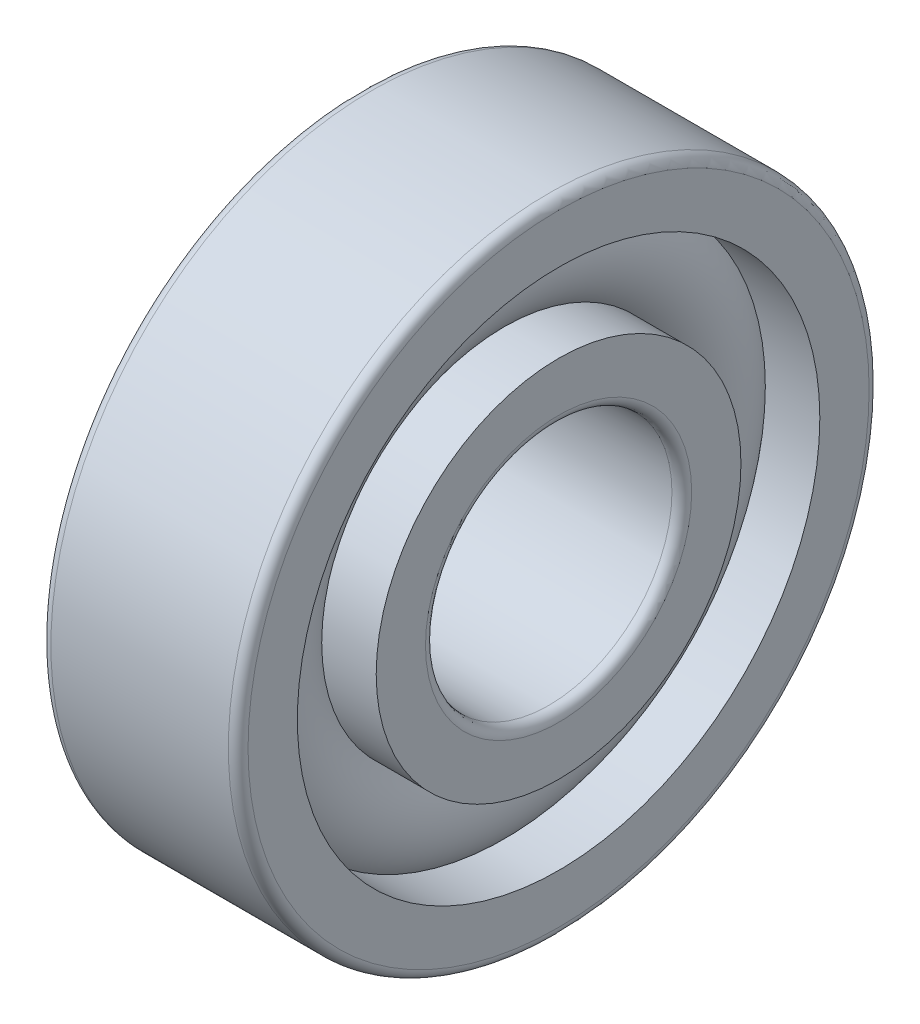
SolidWorks part; units mm, degrees
ref_plane "Plane1" through (0, 0, 0) normal (0, 0, 1) x (1, 0, 0)
ref_plane "Plane2" through (0, 0, 0) normal (0, 1, 0) x (1, 0, 0)
ref_plane "Plane3" through (0, 0, 0) normal (1, 0, 0) x (0, 0, -1)
sketch "Clipboard" plane through (0, 0, 0) normal (0, 0, 1) x (1, 0, 0)
  line L0 (-10, 0) -> (10, 0) construction
  line L1 (0, 0) -> (22.3471, -0.7804)
  line L2 (0, 0) -> (4.4973, 0.157)
  line L3 (0, 0) -> (22.3471, -0.7804)
  line L4 (0, 0) -> (-22.3573, -0.3902)
  dimension "BallCLRad" = 4.5
  dimension "Count" = 2
  dimension "Show_count" = 2
  dimension "Max_count" = 2
  dimension "Min_count" = 1
sketch "CagSpiSke" plane through (0, 0, 0) normal (0, 0, 1) x (1, 0, 0)
  line L0 (0.12, 4.3) -> (0.12, 4.7)
  line L1 (0.12, 4.7) -> (-0.12, 4.7)
  line L2 (-0.12, 4.7) -> (-0.12, 4.3)
  line L3 (-0.12, 4.3) -> (0.12, 4.3)
  line L4 (-20.6375, 0) -> (20.6375, 0) construction
  line L5 (0, 0) -> (0, 23.7692) construction
  dimension "Thickness" = 0.24
  dimension "OD" = 9.4
  dimension "ID" = 8.6
revolve "CageSpine" add sketch "CagSpiSke" angle 0.001 about L4 reverse direction yes
ref_axis "Axis1" through (-50, 0, 0) along (1, 0, 0)
sketch "CagBalSke" plane through (0, 0, 0) normal (0, 0, 1) x (1, 0, 0)
  line L0 (-1.32, 4.5) -> (1.32, 4.5)
  line L1 (-1.905, 4.5) -> (1.905, 4.5) construction
  line L2 (-10, 0) -> (10, 0) construction
  line L3 (0, 0) -> (0, 24) construction
  arc A0 (1.32, 4.5) -> (-1.32, 4.5) centre (0, 4.5) cw
  dimension "CageWallOD" = 2.64
  dimension "BallCLRad" = 4.5
revolve "CageBall" [suppressed] add sketch "CagBalSke" angle 360 about L1 reverse direction yes
pattern_circular "CageBalls" [suppressed] count 2 every 180 about axis through (-50, 0, 0) along (1, 0, 0)
sketch "CagTrmODSke" plane through (0, 0, 0) normal (0, 0, 1) x (1, 0, 0)
  line L0 (1.321, 4.7) -> (1.321, 5.821)
  line L1 (1.321, 5.821) -> (-1.321, 5.821)
  line L2 (-1.321, 5.821) -> (-1.321, 4.7)
  line L3 (-1.321, 4.7) -> (1.321, 4.7)
  line L4 (-20.6375, 0) -> (20.6375, 0) construction
  line L5 (0, 0) -> (0, 25) construction
  dimension "Width" = 2.642
  dimension "ID" = 9.4
  dimension "OD" = 11.642
revolve "CageTrimOD" [suppressed] cut sketch "CagTrmODSke" angle 360 about L4 reverse direction yes
sketch "CagTrmIDSke" plane through (0, 0, 0) normal (0, 0, 1) x (1, 0, 0)
  line L0 (1.321, 3.181) -> (1.321, 4.3)
  line L1 (1.321, 4.3) -> (-1.321, 4.3)
  line L2 (-1.321, 4.3) -> (-1.321, 3.181)
  line L3 (-1.321, 3.181) -> (1.321, 3.181)
  line L4 (-20.6375, 0) -> (20.6375, 0) construction
  line L5 (0, 0) -> (0, 25) construction
  dimension "ID" = 6.362
  dimension "OD" = 8.6
  dimension "Width" = 2.642
revolve "CageTrimID" [suppressed] cut sketch "CagTrmIDSke" angle 360 about L4 reverse direction yes
sketch "BalSimSke" plane through (0, 0, 0) normal (0, 0, 1) x (1, 0, 0)
  line L0 (-10, 0) -> (10, 0) construction
  line L1 (-10, 4.5) -> (10, 4.5) construction
  line L2 (0, 0) -> (0, 23) construction
  circle A0 centre (0, 4.5) radius 1.2
  dimension "Ball_diameter" = 2.4
  dimension "BallCLRad" = 4.5
revolve "BallsSimplified" add sketch "BalSimSke" angle 360 about L0
sketch "BalDetSke" plane through (0, 0, 0) normal (0, 0, 1) x (1, 0, 0)
  line L0 (-1.2, 4.5) -> (1.2, 4.5)
  line L1 (-1.905, 4.5) -> (1.905, 4.5) construction
  line L2 (0, 0) -> (0, 25) construction
  arc A0 (1.2, 4.5) -> (-1.2, 4.5) centre (0, 4.5) cw
  dimension "Ball_diameter" = 2.4
  dimension "BallCLRad" = 4.5
revolve "BallDetailed" [suppressed] add sketch "BalDetSke" angle 360 about L1 reverse direction yes
sketch "InnRacSke" plane through (0, 0, 0) normal (0, 0, 1) x (1, 0, 0)
  line L0 (-0.8606, 3.7) -> (-2, 3.7)
  line L1 (-2, 3.7) -> (-2, 2.7)
  line L2 (-1.8, 2.5) -> (1.8, 2.5)
  line L3 (2, 2.7) -> (2, 3.7)
  line L4 (2, 3.7) -> (0.8606, 3.7)
  line L5 (-20.6375, 0) -> (20.6375, 0) construction
  line L6 (0, 0) -> (0, 30) construction
  arc A0 (-2, 2.7) -> (-1.8, 2.5) centre (-1.8, 2.7) ccw
  arc A1 (1.8, 2.5) -> (2, 2.7) centre (1.8, 2.7) ccw
  arc A2 (0.8606, 3.7) -> (-0.8606, 3.7) centre (0, 4.5) cw
  dimension "Fillet_radius" = 0.2
  dimension "Ball_diameter" = 2.35
  dimension "ID" = 5
  dimension "OD" = 7.4
  dimension "Width" = 4
  dimension "BallCLRad" = 4.5
revolve "InnerRace" add sketch "InnRacSke" angle 360 about L5 reverse direction yes
sketch "OutRacSke" plane through (0, 0, 0) normal (0, 0, 1) x (1, 0, 0)
  line L0 (-0.8606, 5.3) -> (-2, 5.3)
  line L1 (-2, 5.3) -> (-2, 6.3)
  line L2 (-1.8, 6.5) -> (1.8, 6.5)
  line L3 (2, 6.3) -> (2, 5.3)
  line L4 (2, 5.3) -> (0.8606, 5.3)
  line L5 (-20.6375, 0) -> (20.6375, 0) construction
  line L6 (0, 0) -> (0, 30) construction
  arc A0 (-2, 6.3) -> (-1.8, 6.5) centre (-1.8, 6.3) cw
  arc A1 (1.8, 6.5) -> (2, 6.3) centre (1.8, 6.3) cw
  arc A2 (0.8606, 5.3) -> (-0.8606, 5.3) centre (0, 4.5) ccw
  dimension "Fillet_radius" = 0.2
  dimension "Ball_diameter" = 2.35
  dimension "OD" = 13
  dimension "ID" = 10.6
  dimension "Width" = 4
  dimension "BallCLRad" = 4.5
revolve "OuterRace" add sketch "OutRacSke" angle 360 about L5 reverse direction yes
pattern_circular "BallsDetailed" [suppressed] count 2 every 180 about axis through (-50, 0, 0) along (1, 0, 0)
equation "\"BallCLRad@Clipboard\" = ( \"OD@OutRacSke\" + \"ID@InnRacSke\" ) / 4"
equation "\"BallCLRad@BalSimSke\" = \"BallCLRad@Clipboard\""
equation "\"BallCLRad@BalDetSke\" = \"BallCLRad@Clipboard\""
equation "\"BallCLRad@InnRacSke\" = \"BallCLRad@Clipboard\""
equation "\"BallCLRad@OutRacSke\" = \"BallCLRad@Clipboard\""
equation "\"Ball_diameter@InnRacSke\" = \"Ball_diameter@BalDetSke\" - 0.05"
equation "\"Ball_diameter@OutRacSke\" = \"Ball_diameter@BalDetSke\" - 0.05"
equation "\"Ball_diameter@BalSimSke\" = \"Ball_diameter@BalDetSke\""
equation "\"Width@OutRacSke\" = \"Width@InnRacSke\""
equation "\"Fillet_radius@OutRacSke\" = \"Fillet_radius@InnRacSke\""
equation "\"Max_count@Clipboard\" = int( 3.14159265 / atn(( \"Ball_diameter@BalDetSke\" / 2) / sqr( \"BallCLRad@Clipboard\"  *  \"BallCLRad@Clipboard\" - ( \"Ball_diameter@BalDetSke\" / 2) *  ( \"Ball_diameter@BalDetSke\" / 2))))"
equation "\"Max_count@Clipboard\" = ((sgn( \"Max_count@Clipboard\" - \"Count@Clipboard\" )-1)*( \"Max_count@Clipboard\" - \"Count@Clipboard\" ))/-2+ \"Count@Clipboard\""
equation "\"Count@BallsDetailed\" = int( \"Show_count@Clipboard\" ) "
equation "\"Count@BallsDetailed\" = ((sgn( \"Count@BallsDetailed\" - \"Max_count@Clipboard\" )-1)*( \"Count@BallsDetailed\" - \"Max_count@Clipboard\" ))/-2+ \"Max_count@Clipboard\""
equation "\"Count@BallsDetailed\" = ((sgn( \"Count@BallsDetailed\" - \"Min_count@Clipboard\" )+1)*( \"Count@BallsDetailed\" - \"Min_count@Clipboard\"))/2 +\"Min_count@Clipboard\""
equation "\"Angle@BallsDetailed\" = 360.0 / \"Max_count@Clipboard\""
equation "\"BallCLRad@CagBalSke\" = \"BallCLRad@Clipboard\""
equation "\"Count@CageBalls\" = \"Count@BallsDetailed\""
equation "\"Angle@CageBalls\" = \"Angle@BallsDetailed\""
equation "\"Angle@CageSpine\" =  \"Angle@CageBalls\" * ( \"Count@CageBalls\" -1 + int( \"Count@CageBalls\" / \"Max_count@Clipboard\" ) )  + 0.001 -  int( \"Count@CageBalls\" / \"Max_count@Clipboard\" ) * 0.001"
equation "\"Angle@CageSpine\" =  \"Angle@CageSpine\" * int( \"Min_count@Clipboard\" / 2) + int(1 / \"Min_count@Clipboard\")  * 0.001"
equation "\"CageWallOD@CagBalSke\" =  \"Ball_diameter@BalDetSke\" * 1.1"
equation "\"Thickness@CagSpiSke\" =  \"Ball_diameter@BalDetSke\" * 0.1"
equation "\"OD@CagTrmODSke\" = \"BallCLRad@Clipboard\" * 2 + \"CageWallOD@CagBalSke\" + 0.002"
equation "\"ID@CagTrmODSke\" = \"BallCLRad@Clipboard\" * 2 + \"Ball_diameter@BalDetSke\" / 6"
equation "\"OD@CagTrmIDSke\" = \"BallCLRad@Clipboard\" * 2 - \"Ball_diameter@BalDetSke\" / 6"
equation "\"ID@CagTrmIDSke\" = \"BallCLRad@Clipboard\" * 2 - \"CageWallOD@CagBalSke\" + 0.002"
equation "\"OD@CagSpiSke\" = \"ID@CagTrmODSke\""
equation "\"ID@CagSpiSke\" = \"OD@CagTrmIDSke\""
equation "\"Width@CagTrmODSke\" = \"CageWallOD@CagBalSke\" + 0.002"
equation "\"Width@CagTrmIDSke\" = \"CageWallOD@CagBalSke\" + 0.002"
